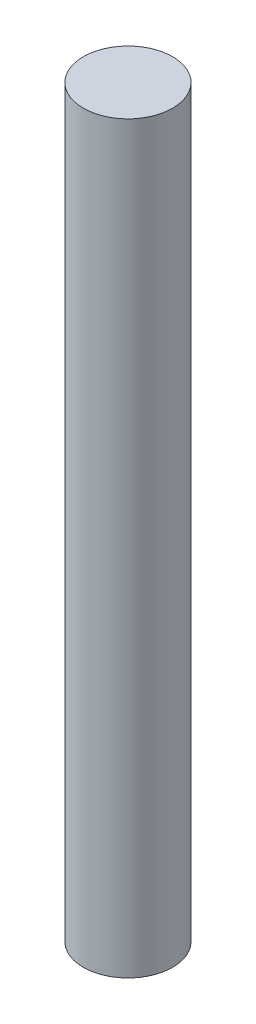
SolidWorks part; units mm, degrees
ref_plane "Front Plane" through (0, 0, 0) normal (0, 0, 1) x (1, 0, 0)
ref_plane "Top Plane" through (0, 0, 0) normal (0, 1, 0) x (1, 0, 0)
ref_plane "Right Plane" through (0, 0, 0) normal (1, 0, 0) x (0, 0, -1)
sketch "SK Stainless sheath" plane through (0, 0, 0) normal (0, 1, 0) x (1, 0, 0)
  circle A0 centre (0, 0) radius 3
extrude "Stainless sheath" add sketch "SK Stainless sheath" along normal blind 50 separate body
sketch "SK Sleeve" plane through (0, 0, 0) normal (0, 1, 0) x (1, 0, 0)
  circle A0 centre (0, 0) radius 2.5
extrude "Sleeve" [suppressed] add sketch "SK Sleeve" along normal blind 12 from offset 50 separate body
sketch "SK Cable" plane through (0, 0, 0) normal (0, 1, 0) x (1, 0, 0)
  circle A0 centre (0, 0) radius 2
extrude "Cable" [suppressed] add sketch "SK Cable" along normal blind 38 from offset 62 separate body
sketch "SK Wire red VDD" plane through (0, 0, 0) normal (0, 1, 0) x (1, 0, 0)
  circle A0 centre (-1.1, -0.6) radius 0.55
extrude "Wire red VDD" [suppressed] add sketch "SK Wire red VDD" along normal blind 12 from offset 100 separate body
sketch "SK Wire black GND" plane through (0, 0, 0) normal (0, 1, 0) x (1, 0, 0)
  circle A0 centre (1.1, -0.6) radius 0.55
extrude "Wire black GND" [suppressed] add sketch "SK Wire black GND" along normal blind 12 from offset 100 separate body
sketch "SK Wire yellow DQ" plane through (0, 0, 0) normal (0, 1, 0) x (1, 0, 0)
  circle A0 centre (0, 1.1) radius 0.55
extrude "Wire yellow DQ" [suppressed] add sketch "SK Wire yellow DQ" along normal blind 12 from offset 100 separate body
